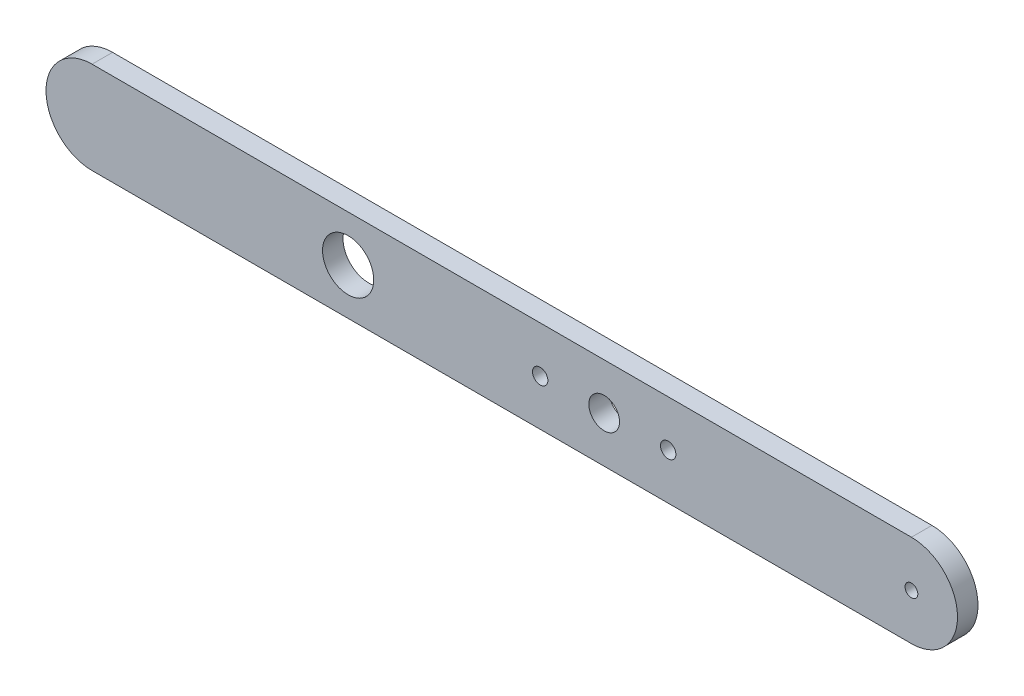
SolidWorks part; units mm, degrees
ref_plane "正面" through (0, 0, 0) normal (0, 0, 1) x (1, 0, 0)
ref_plane "平面" through (0, 0, 0) normal (0, 1, 0) x (1, 0, 0)
ref_plane "右側面" through (0, 0, 0) normal (1, 0, 0) x (0, 0, -1)
sketch "ｽｹｯﾁ1" plane through (0, 0, 0) normal (0, 0, 1) x (1, 0, 0)
  line L0 (0, 0) -> (160, 0) construction
  line L1 (0, 9) -> (160, 9)
  line L2 (0, -9) -> (160, -9)
  arc A0 (0, 9) -> (0, -9) centre (0, 0) ccw
  arc A1 (160, -9) -> (160, 9) centre (160, 0) ccw
  circle A2 centre (160, 0) radius 1.25
  circle A3 centre (100, 0) radius 3
  circle A5 centre (50, 0) radius 5
  point P3 (80, 0)
  point P14 (0, 0)
  dimension "D2" = 2.5
  dimension "D3" = 9
  dimension "D4" = 6
  dimension "D6" = 10
  dimension "D7" = 50
  dimension "D1" = 60
  dimension "D5" = 100
extrude "ﾎﾞｽ - 押し出し1" add sketch "ｽｹｯﾁ1" along normal blind 4
sketch "ｽｹｯﾁ2" plane through (0, 0, 4) normal (0, 0, 1) x (1, 0, 0)
  line L0 (100, 0) -> (100, -9) construction
  line L1 (0, -9) -> (160, -9) construction
  line L2 (87.5, 0) -> (112.5, 0) construction
  circle A0 centre (112.5, 0) radius 1.5
  circle A1 centre (87.5, 0) radius 1.5
  dimension "D2" = 3
  dimension "D1" = 25
extrude "ｶｯﾄ - 押し出し1" cut sketch "ｽｹｯﾁ2" against normal through all
